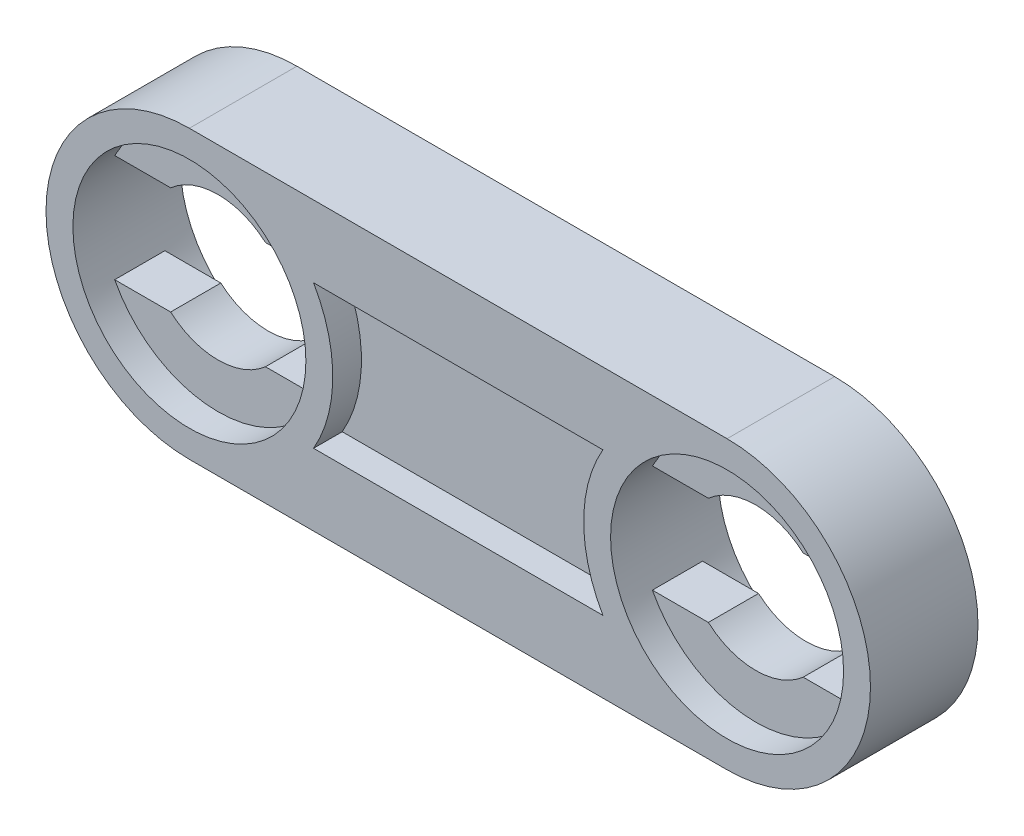
SolidWorks part; units mm, degrees
ref_plane "前视基准面" through (0, 0, 0) normal (0, 0, 1) x (1, 0, 0)
ref_plane "上视基准面" through (0, 0, 0) normal (0, 1, 0) x (1, 0, 0)
ref_plane "右视基准面" through (0, 0, 0) normal (1, 0, 0) x (0, 0, -1)
sketch "草图1" plane through (0, 0, 0) normal (0, 0, 1) x (1, 0, 0)
  line L1 (0, 4) -> (15, 4)
  line L3 (0, -4) -> (15, -4)
  arc A0 (0, 4) -> (0, -4) centre (0, 0) ccw
  arc A3 (15, -4) -> (15, 4) centre (15, 0) ccw
extrude "凸台-拉伸1" add sketch "草图1" against normal blind 3
sketch "草图2" plane through (0, 0, 0) normal (0, 0, 1) x (1, 0, 0)
  line L0 (1.3229, -1.5) -> (2.8831, -1.5)
  line L1 (-2.8831, -1.5) -> (-1.3229, -1.5)
  line L2 (1.3229, 1.5) -> (2.8831, 1.5)
  line L3 (-2.8831, 1.5) -> (-1.3229, 1.5)
  arc A0 (1.3229, 1.5) -> (-1.3229, 1.5) centre (0, 0) ccw
  arc A1 (-2.8831, 1.5) -> (-2.8831, -1.5) centre (0, 0) ccw
  arc A3 (2.8831, -1.5) -> (2.8831, 1.5) centre (0, 0) ccw
  arc A4 (-1.3229, -1.5) -> (1.3229, -1.5) centre (0, 0) ccw
extrude "切除-拉伸1" cut sketch "草图2" against normal up to next
sketch "草图3" plane through (0, 0, 0) normal (0, 0, 1) x (1, 0, 0)
  circle A1 centre (0, 0) radius 3.25
extrude "切除-拉伸2" cut sketch "草图3" against normal blind 0.8
extrude "切除-拉伸3" cut sketch "草图3<2>" along normal blind 0.8 from offset 3 offset against normal yes
sketch "草图3<2>" plane through (0, 0, 0) normal (0, 0, 1) x (1, 0, 0) same geometry as "草图3"
ref_plane "基准面1" through (7.5, 0, 0) normal (1, 0, 0) x (0, 0, -1)
mirror "镜向1" about plane through (7.5, 0, 0) normal (1, 0, 0) of "切除-拉伸3", "切除-拉伸2", "切除-拉伸1"
sketch "草图4" plane through (0, 0, 0) normal (0, 0, 1) x (1, 0, 0)
  line L0 (3.4641, 2) -> (11.5359, 2)
  line L2 (3.4641, -2) -> (11.5359, -2)
  arc A0 (3.4641, -2) -> (3.4641, 2) centre (0, 0) ccw
  arc A1 (11.5359, 2) -> (11.5359, -2) centre (15, 0) ccw
extrude "切除-拉伸4" cut sketch "草图4" against normal blind 0.8
sketch "草图5" plane through (0, 0, -3) normal (0, 0, -1) x (-1, 0, 0)
  line L1 (-11, -2) -> (-4, -2)
  line L2 (-11, -2) -> (-11, 2)
  line L3 (-11, 2) -> (-4, 2)
  line L4 (-4, -2) -> (-4, 2)
extrude "切除-拉伸5" cut sketch "草图5" against normal blind 0.8
